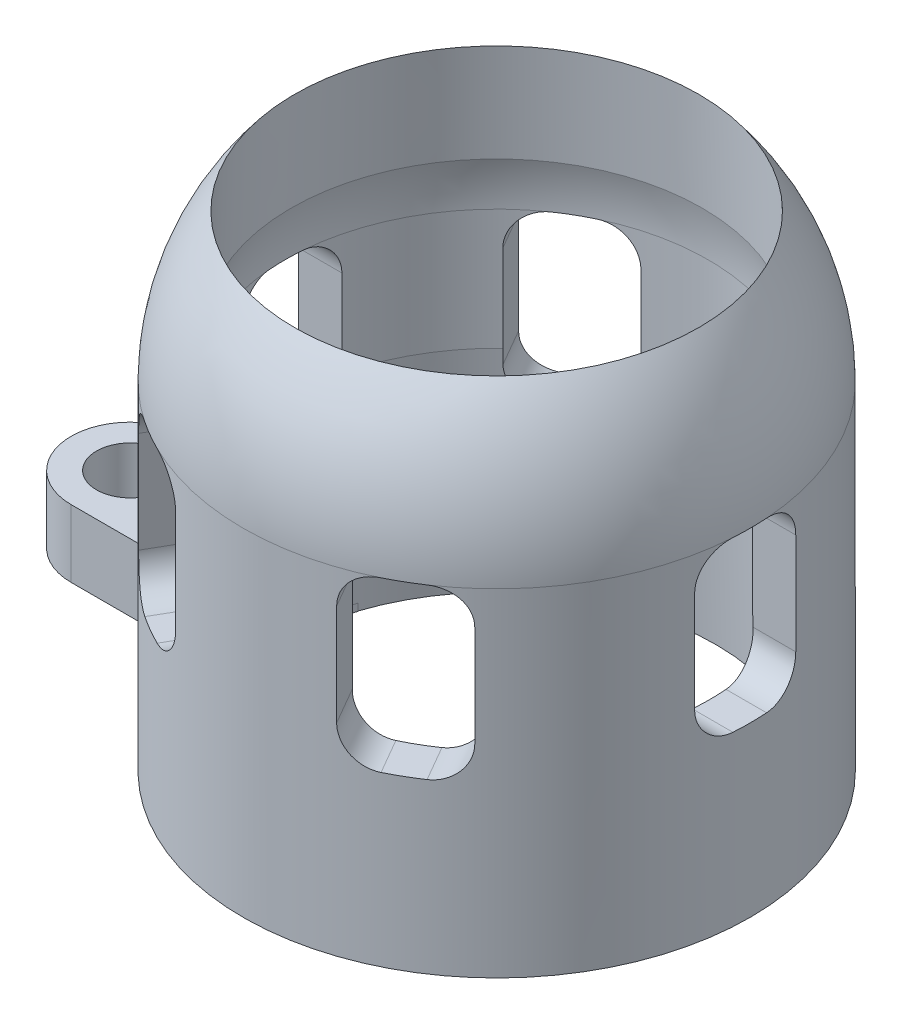
SolidWorks part; units mm, degrees
ref_plane "Front Plane" through (0, 0, 0) normal (0, 0, 1) x (1, 0, 0)
ref_plane "Top Plane" through (0, 0, 0) normal (0, 1, 0) x (1, 0, 0)
ref_plane "Right Plane" through (0, 0, 0) normal (1, 0, 0) x (0, 0, -1)
sketch "Sketch3" plane through (0, 0, 0) normal (0, 0, 1) x (1, 0, 0)
  line L0 (-6.2755, 0.0036) -> (-6.2755, 10.0036)
  line L1 (-7.5255, 0.0036) -> (-7.5255, 10.0036)
  line L2 (-7.5255, 0.0036) -> (-6.2755, 0.0036)
  line L3 (0, 17.06) -> (0, 15.8126)
  line L4 (0, 15.8126) -> (-0.0803, 15.8126)
  arc A0 (0, 17.06) -> (-7.5255, 10.0036) centre (-0.4545, 10.0036) ccw
  arc A1 (-0.0803, 15.8126) -> (-6.2755, 10.0036) centre (-0.4545, 10.0036) ccw
  dimension "D1" = 1.25
  dimension "D2" = 10
revolve "Revolve1" add sketch "Sketch3" angle 360 about L3
sketch "Sketch4" plane through (0, 0, 0) normal (0, 1, 0) x (1, 0, 0)
  circle A0 centre (0, 0) radius 6.5
extrude "Cut-Extrude2" cut sketch "Sketch4" along normal blind 22 draft 2
ref_plane "Plane1" through (-7.5255, 0, 0) normal (-1, 0, 0) x (0, 0, 1)
sketch "Sketch5" plane through (-7.5255, 0, 0) normal (-1, 0, 0) x (0, 0, 1)
  line L0 (0, 10.0036) -> (0, 0) construction
  line L1 (7.5255, 10.0036) -> (-7.5255, 10.0036) construction
  line L2 (-7.5255, 5.0036) -> (7.5255, 5.0036) construction
  line L3 (-7.5255, 10.0036) -> (-7.5255, 0.0036) construction
  line L4 (7.5255, 0.0036) -> (7.5255, 10.0036) construction
  line L5 (1.5, 10.0036) -> (1.5, 0) construction
  line L6 (-1.5, 10.0036) -> (-1.5, 0) construction
  line L8 (-1.5, 10.0036) -> (1.5, 10.0036)
  line L9 (-1.5, 10.0036) -> (-1.5, 5.0018)
  line L10 (-1.5, 5.0018) -> (1.5, 5.0018)
  line L11 (1.5, 10.0036) -> (1.5, 5.0018)
  dimension "D1" = 1.5
  dimension "D2" = 1.5
extrude "Cut-Extrude3" cut sketch "Sketch5" against normal blind 2
ref_point "Point1"
ref_axis "Axis1" through (0, 14.3941, 0) along (0, 1, 0)
fillet "Fillet1" radius 1 4 edges at (-6.7597, 5.0018, 1.5) (-6.7597, 5.0018, -1.5) (-6.7341, 10.0036, 1.5) (-6.7341, 10.0036, -1.5)
pattern_circular "CirPattern1" count 6 over 360 about axis through (0, 14.3941, 0) along (0, 1, 0) of "Cut-Extrude3", "Fillet1"
sketch "Sketch6" plane through (0, 0, 0) normal (0, 1, 0) x (1, 0, 0)
  line L0 (-11.1625, 1.2888) -> (-11.1625, 2.0439)
  line L1 (-6.1625, 2.0439) -> (-11.1625, 2.0439)
  line L3 (-6.3249, -1.4663) -> (-11.1625, -1.4663)
  line L4 (-11.5711, 1.2015) -> (-11.8796, 1.8907)
  arc A0 (-6.1625, 2.0439) -> (-6.3249, -1.4663) centre (0, 0) ccw
  arc A1 (-11.8796, 1.8907) -> (-11.1625, -1.4663) centre (-11.1625, 0.2888) ccw
  arc A2 (-11.5711, 1.2015) -> (-11.1625, 1.2888) centre (-11.1625, 0.2888) ccw
  dimension "D1" = 5
extrude "Boss-Extrude2" add sketch "Sketch6" along normal blind 2
fillet "Fillet2" radius 1.5 3 edges at (-7.2426, 1.0018, -2.0439) (-7.3813, 1.0018, 1.4663) (-7.5197, 2, -0.297)
